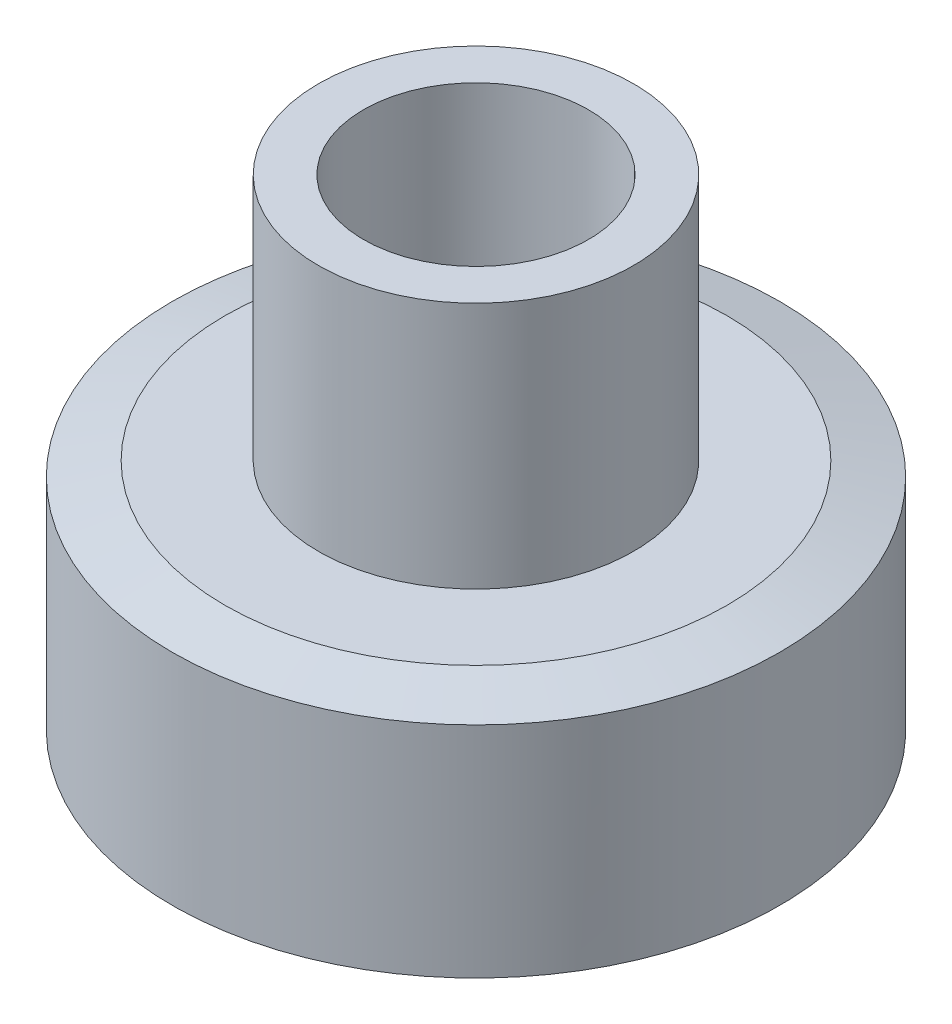
SolidWorks part; units mm, degrees
material "Сталь ШХ15 ГОСТ 801-78"
ref_plane "Plane1" through (0, 0, 0) normal (0, 0, 1) x (1, 0, 0)
ref_plane "Plane2" through (0, 0, 0) normal (0, 1, 0) x (1, 0, 0)
ref_plane "Plane3" through (0, 0, 0) normal (1, 0, 0) x (0, 0, -1)
sketch "Эскиз2" plane through (0, 0, 0) normal (0, 0, 1) x (1, 0, 0)
  line L0 (0, 0) -> (6.75, 0)
  line L1 (6.75, 0) -> (6.75, 5.5)
  line L2 (6.75, 5.5) -> (3.5, 5.5)
  line L3 (3.5, 5.5) -> (3.5, 11)
  line L4 (3.5, 11) -> (0, 11)
  line L5 (0, 11) -> (0, 0)
  dimension "D1" = 6.75
  dimension "D2" = 5.5
  dimension "D3" = 5.5
  dimension "D4" = 3.5
ref_axis "Ось1" through (0, 11, 0) along (0, -1, 0)
revolve "Повернуть2" add sketch "Эскиз2" angle 360 about axis through (0, 11, 0) along (0, -1, 0)
chamfer "Фаска2" distance 1.175 angle 15 1 edges at (-6.75, 5.5, 0) first distance on face at (-3.5, 5.5, 0)
chamfer "Фаска3" distance 1.175 angle 15 1 edges at (-6.75, 0, 0) first distance on face at (-6.75, 0, 0)
sketch "Эскиз4" plane through (0, 11, 0) normal (0, 1, 0) x (1, 0, 0)
  circle A0 centre (0, 0) radius 2.5
  dimension "D1" = 5
extrude "Вырез-Вытянуть2" cut sketch "Эскиз4" against normal through all both contours A0
